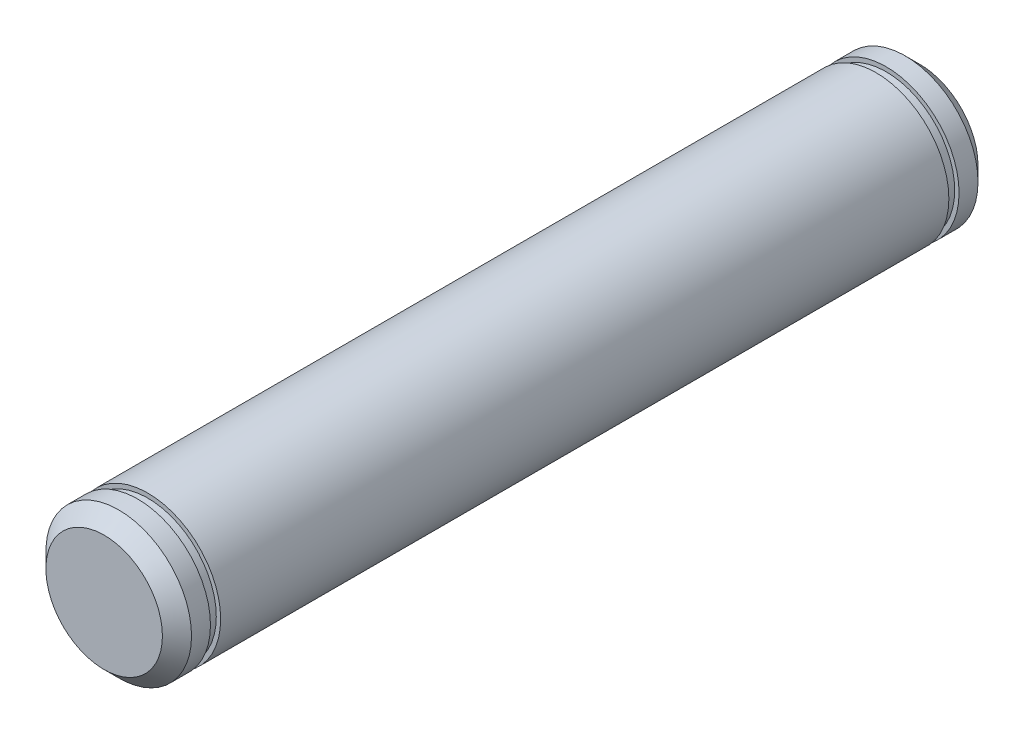
SolidWorks part; units mm, degrees
ref_plane "Front Plane" through (0, 0, 0) normal (0, 0, 1) x (1, 0, 0)
ref_plane "Top Plane" through (0, 0, 0) normal (0, 1, 0) x (1, 0, 0)
ref_plane "Right Plane" through (0, 0, 0) normal (1, 0, 0) x (0, 0, -1)
sketch "Sketch1" plane through (0, 0, 0) normal (0, 0, 1) x (1, 0, 0)
  circle A0 centre (0, 0) radius 5
  dimension "D1" = 10
extrude "Boss-Extrude1" add sketch "Sketch1" along normal blind 28 and the other way blind 28
ref_plane "Plane1" through (0, 0, 25) normal (0, 0, 1) x (1, 0, 0)
sketch "Sketch2" plane through (0, 0, 25) normal (0, 0, 1) x (1, 0, 0)
  circle A0 centre (0, 0) radius 4.7
  dimension "D1" = 9.4
extrude "Cut-Extrude-Thin1" cut sketch "Sketch2" along normal blind 0.7 thin thin type one direction wall 10
mirror "Mirror1" about plane through (0, 0, 0) normal (0, 0, 1) of "Cut-Extrude-Thin1"
chamfer "Chamfer1" distance 1 angle 45 2 edges at (5, 0, -28) (5, 0, 28)
